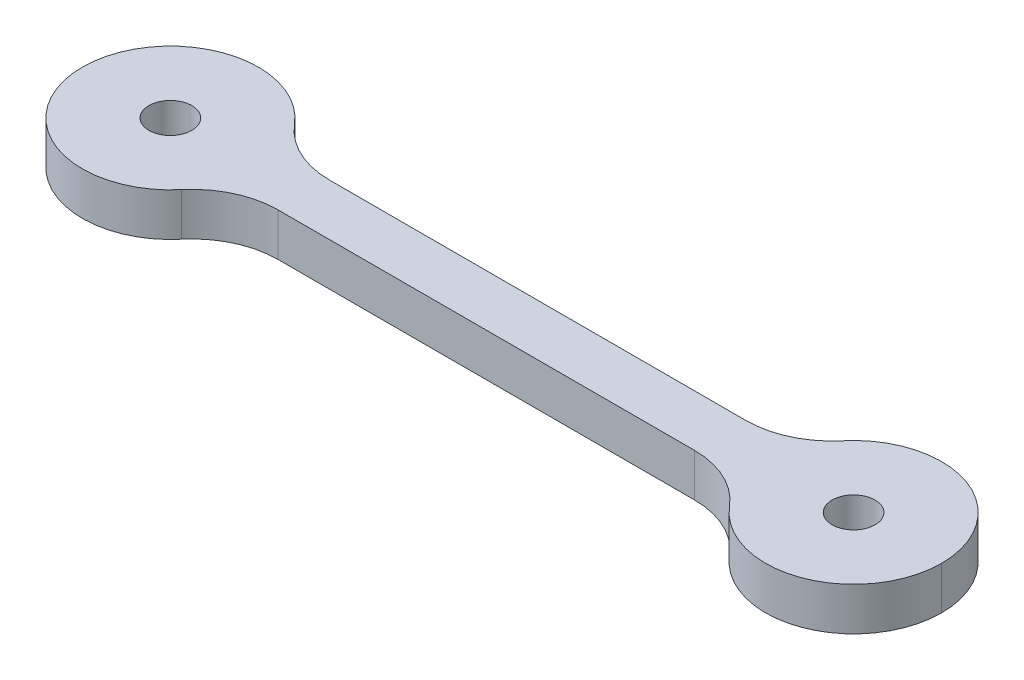
SolidWorks part; units mm, degrees
ref_plane "Front Plane" through (0, 0, 0) normal (0, 0, 1) x (1, 0, 0)
ref_plane "Top Plane" through (0, 0, 0) normal (0, 1, 0) x (1, 0, 0)
ref_plane "Right Plane" through (0, 0, 0) normal (1, 0, 0) x (0, 0, -1)
sketch "Sketch1" plane through (0, 0, 0) normal (0, 1, 0) x (1, 0, 0)
  line L0 (0, 10.25) -> (100, 10.25) construction
  line L1 (0, 0) -> (100, 0)
  line L2 (0, 0) -> (0, 20.5)
  line L3 (0, 20.5) -> (100, 20.5)
  line L4 (100, 0) -> (100, 20.5)
  line L5 (50, 20.5) -> (50, 0) construction
  circle A0 centre (10.25, 10.25) radius 2.5
  circle A9 centre (89.75, 10.25) radius 2.5
  dimension "D3" = 5
  dimension "D1" = 100
  dimension "D2" = 20.5
  dimension "D5" = 10.25
extrude "Boss-Extrude1" add sketch "Sketch1" along normal blind 5
fillet "Fillet1" radius 10.25 4 edges at (0, 2.5, 0) (0, 2.5, -20.5) (100, 2.5, -20.5) (100, 2.5, 0)
sketch "Sketch2" plane through (0, 5, 0) normal (0, 1, 0) x (1, 0, 0)
  line L0 (50, 20.5) -> (50, 0) construction
  line L1 (89.75, 20.5) -> (10.25, 20.5) construction
  line L2 (10.25, 0) -> (89.75, 0) construction
  line L3 (0, 10.25) -> (100, 10.25) construction
  line L4 (10.25, 20.5) -> (10.25, 10.25) construction
  line L5 (20.0511, 13.25) -> (79.9489, 13.25)
  line L6 (20.0511, 7.25) -> (79.9489, 7.25)
  line L7 (10.25, 0) -> (89.75, 0)
  line L8 (10.25, 20.5) -> (89.75, 20.5)
  arc A0 (20.0511, 13.25) -> (10.25, 20.5) centre (10.25, 10.25) ccw
  arc A1 (10.25, 0) -> (20.0511, 7.25) centre (10.25, 10.25) ccw
  arc A2 (89.75, 0) -> (79.9489, 7.25) centre (89.75, 10.25) cw
  arc A3 (79.9489, 13.25) -> (89.75, 20.5) centre (89.75, 10.25) cw
  point P23 (50, 7.25)
  point P24 (50, 13.25)
  dimension "D1" = 3
extrude "Cut-Extrude1" cut sketch "Sketch2" against normal blind 10
fillet "Fillet2" radius 10 4 edges at (79.9489, 2.5, -13.25) (20.0511, 2.5, -13.25) (79.9489, 2.5, -7.25) (20.0511, 2.5, -7.25)
